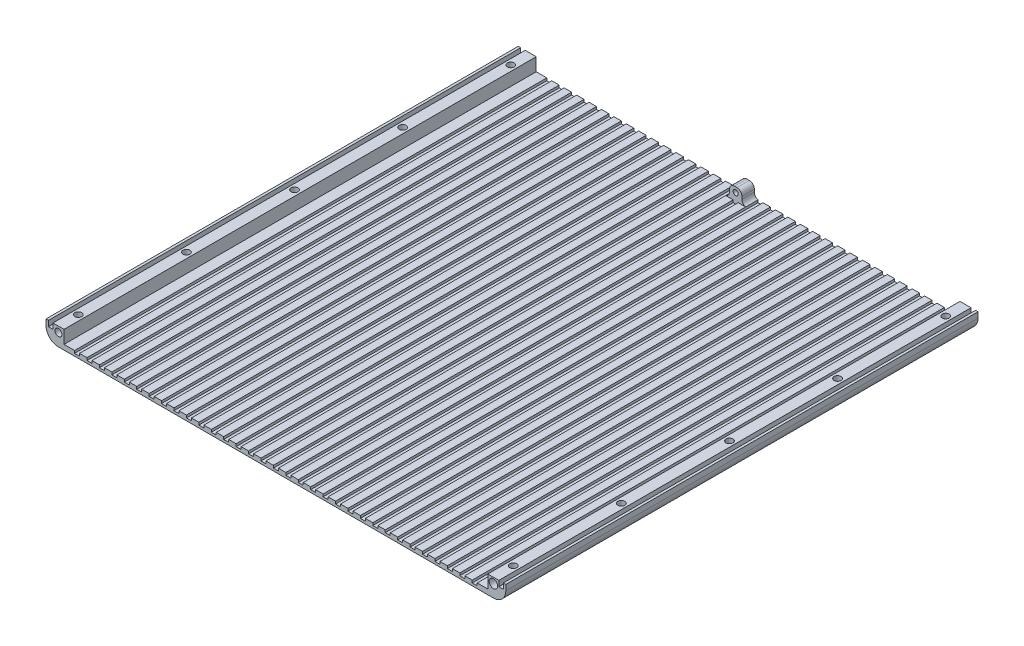
SolidWorks part; units mm, degrees
ref_plane "Front Plane" through (0, 0, 0) normal (0, 0, 1) x (1, 0, 0)
ref_plane "Top Plane" through (0, 0, 0) normal (0, 1, 0) x (1, 0, 0)
ref_plane "Right Plane" through (0, 0, 0) normal (1, 0, 0) x (0, 0, -1)
sketch "Sketch1" plane through (0, 0, 0) normal (0, 0, 1) x (1, 0, 0)
  line L0 (-93.3602, 1.0883) -> (-93.3602, 3.3383)
  line L1 (-93.3602, 3.3383) -> (-86.1102, 3.3383)
  line L2 (-86.1102, 3.3383) -> (-86.1102, -1.9117)
  line L3 (-86.1102, -1.9117) -> (84.3898, -1.9117)
  line L4 (84.3898, -1.9117) -> (84.3898, 3.3383)
  line L5 (84.3898, 3.3383) -> (91.6398, 3.3383)
  line L6 (91.6398, 3.3383) -> (91.6398, 1.0883)
  line L7 (-88.3602, -3.9117) -> (86.6398, -3.9117)
  line L8 (-0.8602, -1.9117) -> (-0.8602, -3.9117) construction
  arc A0 (86.6398, -3.9117) -> (91.6398, 1.0883) centre (86.6398, 1.0883) ccw
  arc A1 (-88.3602, -3.9117) -> (-93.3602, 1.0883) centre (-88.3602, 1.0883) cw
  dimension "D1" = 170.5
  dimension "D2" = 175
  dimension "D3" = 7.25
  dimension "D4" = 5.25
extrude "Boss-Extrude1" add sketch "Sketch1" along normal blind 190
sketch "Sketch2" plane through (0, 3.3383, 0) normal (0, 1, 0) x (1, 0, 0)
  line L0 (-0.8602, 0) -> (-0.8602, -190) construction
  line L1 (-93.3602, -190) -> (-93.3602, 0) construction
  line L2 (84.3898, 0) -> (-86.1102, 0) construction
  line L3 (84.3898, -190) -> (-86.1102, -190) construction
  line L5 (91.6398, -190) -> (91.6398, 0) construction
  line L7 (-93.3602, -95) -> (91.6398, -95) construction
  circle A0 centre (-88.3602, -8) radius 1.4
  circle A1 centre (-88.3602, -182) radius 1.4
  circle A2 centre (86.6398, -8) radius 1.4
  circle A3 centre (86.6398, -182) radius 1.4
  circle A4 centre (-88.3602, -95) radius 1.4
  circle A5 centre (86.6398, -95) radius 1.4
  circle A6 centre (-88.3602, -51.5) radius 1.4
  circle A7 centre (-88.3602, -138.5) radius 1.4
  circle A8 centre (86.6398, -51.5) radius 1.4
  circle A9 centre (86.6398, -138.5) radius 1.4
  dimension "D1" = 2.8
  dimension "D2" = 87
  dimension "D3" = 87
  dimension "D4" = 5
  dimension "D5" = 43.5
  dimension "D6" = 43.5
extrude "Cut-Extrude1" cut sketch "Sketch2" against normal blind 6
sketch "Sketch3" plane through (0, -1.9117, 0) normal (0, 1, 0) x (1, 0, 0)
  line L0 (-0.8602, 0) -> (-0.8602, -190) construction
  line L1 (84.3898, 0) -> (-86.1102, 0) construction
  line L2 (84.3898, -190) -> (-86.1102, -190) construction
  line L3 (-0.8602, 0) -> (-0.8602, -190) construction
  line L4 (-1.8602, -190) -> (0.1398, -190)
  line L5 (-1.8602, -190) -> (-1.8602, 0)
  line L6 (-1.8602, 0) -> (0.1398, 0)
  line L7 (0.1398, -190) -> (0.1398, 0)
  dimension "D1" = 2
extrude "Cut-Extrude2" cut sketch "Sketch3" against normal blind 1
pattern_linear "LPattern1" count 17 spacing 5 along (1, 0, 0) count 17 spacing 5 along (-1, 0, 0) of "Cut-Extrude2"
sketch "Sketch6" plane through (0, 3.3383, 0) normal (0, 1, 0) x (1, 0, 0)
  line L0 (-86.1102, 0) -> (-93.3602, 0) construction
  line L1 (-92.3602, 0) -> (-90.5602, 0)
  line L2 (-92.3602, 0) -> (-92.3602, -190)
  line L3 (-92.3602, -190) -> (-90.5602, -190)
  line L4 (-90.5602, 0) -> (-90.5602, -190)
  line L5 (91.6398, 0) -> (84.3898, 0) construction
  line L6 (88.8398, 0) -> (90.6398, 0)
  line L7 (88.8398, 0) -> (88.8398, -190)
  line L8 (88.8398, -190) -> (90.6398, -190)
  line L9 (90.6398, 0) -> (90.6398, -190)
  line L10 (91.6398, -190) -> (84.3898, -190) construction
  line L11 (-86.1102, -190) -> (-93.3602, -190) construction
  line L12 (91.6398, -190) -> (91.6398, 0) construction
  line L13 (-93.3602, -190) -> (-93.3602, 0) construction
  dimension "D1" = 1.8
  dimension "D2" = 1
  dimension "D3" = 1
extrude "Cut-Extrude3" cut sketch "Sketch6" against normal blind 2.2
sketch "Sketch7" plane through (0, 0, 190) normal (0, 0, 1) x (1, 0, 0)
  line L0 (-86.1102, 3.3383) -> (-90.5602, 3.3383) construction
  line L1 (-86.1102, -1.9117) -> (-86.1102, 3.3383) construction
  line L2 (84.3898, 3.3383) -> (84.3898, -1.9117) construction
  circle A0 centre (-88.3602, 1.0883) radius 1.4
  circle A1 centre (86.6398, 1.0883) radius 1.7184
  point P8 (84.3898, 0.7133)
  dimension "D1" = 2.8
  dimension "D2" = 2.25
  dimension "D3" = 2.25
  dimension "D4" = 2.25
extrude "Cut-Extrude4" cut sketch "Sketch7" against normal blind 4
extrude "Cut-Extrude5" cut sketch "Sketch7<2>" along normal blind 4 from surface starting at face at (-0.8602, -1.9909, 0)
sketch "Sketch7<2>" plane through (0, 0, 190) normal (0, 0, 1) x (1, 0, 0) same geometry as "Sketch7"
sketch "Sketch8" plane through (0, -1.9117, 0) normal (0, 1, 0) x (1, 0, 0)
  line L0 (-93.3602, 0) -> (91.6398, 0) construction
  line L1 (-0.8602, 0) -> (-0.8602, -190) construction
  line L2 (-1.8602, -190) -> (0.1398, -190) construction
  line L4 (-0.8602, -0.5758) -> (-0.8602, -5) construction
  line L5 (-3.3602, 0) -> (1.6398, 0)
  line L6 (-3.3602, 0) -> (-3.3602, -5)
  line L7 (-3.3602, -5) -> (1.6398, -5)
  line L8 (-0.8602, -4.2469) -> (-0.8602, 0) construction
  line L9 (1.6398, 0) -> (1.6398, -5)
  dimension "D1" = 5
  dimension "D2" = 5
extrude "Boss-Extrude2" add sketch "Sketch8" along normal blind 5
sketch "Sketch9" plane through (0, 0, 0) normal (0, 0, -1) x (-1, 0, 0)
  line L1 (-0.1398, -1.9117) -> (1.8602, -1.9117)
  line L2 (-0.1398, -1.9117) -> (-0.1398, -2.9117)
  line L3 (-0.1398, -2.9117) -> (1.8602, -2.9117)
  line L4 (1.8602, -1.9117) -> (1.8602, -2.9117)
extrude "Boss-Extrude3" add sketch "Sketch9" against normal up to surface (5 mm away) up to face at (-0.8602, -0.2451, 5)
fillet "Fillet1" radius 2 4 edges at (-3.3602, 3.0883, 2.5) (-3.3602, -1.9117, 2.5) (1.6398, 3.0883, 2.5) (1.6398, -1.9117, 2.5)
sketch "Sketch10" plane through (0, 0, 0) normal (0, 0, -1) x (-1, 0, 0)
  line L0 (0.8602, 3.0883) -> (0.8602, -3.9117) construction
  line L1 (0.3602, 3.0883) -> (1.3602, 3.0883) construction
  line L2 (88.3602, -3.9117) -> (-86.6398, -3.9117) construction
  circle A0 centre (0.8602, 1.0883) radius 1.0151
  dimension "D1" = 5
extrude "Cut-Extrude6" cut sketch "Sketch10" against normal through all
